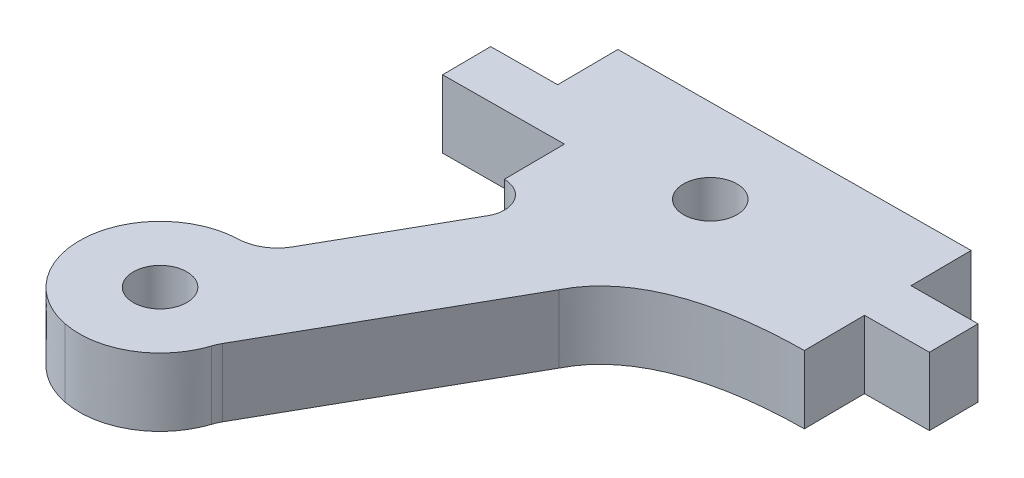
SolidWorks part; units mm, degrees
material "Acrylic (Medium-high impact)"
ref_plane "Front Plane" through (0, 0, 0) normal (0, 0, 1) x (1, 0, 0)
ref_plane "Top Plane" through (0, 0, 0) normal (0, 1, 0) x (1, 0, 0)
ref_plane "Right Plane" through (0, 0, 0) normal (1, 0, 0) x (0, 0, -1)
sketch "Sketch1" plane through (0, 0, 0) normal (0, 1, 0) x (1, 0, 0)
  line L0 (-5.4445, 9.8377) -> (-5.4416, 9.8377)
  line L1 (-5.4416, 9.8377) -> (-5.4208, 7.005)
  line L2 (-5.4208, 7.005) -> (-5.4208, 7.003)
  line L3 (-5.4208, 7.003) -> (-8.531, 6.9802)
  line L4 (-8.531, 6.9802) -> (-8.5144, 4.7142)
  line L5 (-8.5144, 4.7142) -> (-2.8595, 4.7556)
  line L6 (-2.8595, 4.7556) -> (-2.8388, 1.9229)
  line L7 (-1.7504, 0.0661) -> (-5.0527, -5.7627)
  line L8 (-2.7802, -11.3155) -> (2.9162, -1.2617)
  line L9 (14.1054, 4.8606) -> (14.0886, 7.1481)
  line L10 (14.0886, 7.1481) -> (10.9784, 7.1253)
  line L11 (10.9784, 7.1253) -> (10.9577, 9.9577)
  line L12 (10.9577, 9.9577) -> (-5.4445, 9.8377)
  line L13 (3.6635, 6.8214) -> (1.9104, 5.0391) construction
  line L14 (-7.4079, -9.6147) -> (-5.6288, -11.3711) construction
  line L15 (11.0897, 4.8386) -> (14.1054, 4.8606)
  line L16 (11.0897, 4.8386) -> (11.1104, 2.0059)
  circle A0 centre (2.7869, 5.9303) radius 1.25
  circle A1 centre (-6.5183, -10.4929) radius 1.25
  spline S0 degree 3 poles (-2.8388, 1.9229) (-2.3954, 1.9264) (-1.984, 1.6924) (-1.7594, 1.3093) knots 7 7 7 7 8 8 8 8
  spline S1 degree 3 poles (-1.7594, 1.3093) (-1.5349, 0.9265) (-1.5315, 0.4525) (-1.7504, 0.0661) knots 8 8 8 8 9 9 9 9
  spline S2 degree 3 poles (-5.0527, -5.7627) (-5.3774, -6.3357) (-5.9766, -6.6977) (-6.6341, -6.7181) knots 10 10 10 10 11 11 11 11
  spline S3 degree 3 poles (-6.6341, -6.7181) (-8.5475, -6.7772) (-10.1131, -8.2636) (-10.2745, -10.1746) knots 11 11 11 11 12 12 12 12
  spline S4 degree 3 poles (-10.2745, -10.1746) (-10.4358, -12.0857) (-9.1421, -13.8145) (-7.2656, -14.1949) knots 12 12 12 12 13 13 13 13
  spline S5 degree 3 poles (-7.2656, -14.1949) (-5.3893, -14.5752) (-3.5261, -13.4866) (-2.9333, -11.6629) knots 13 13 13 13 14 14 14 14
  spline S6 degree 3 poles (-2.9333, -11.6629) (-2.894, -11.5423) (-2.8428, -11.426) (-2.7802, -11.3155) knots 14 14 14 14 15 15 15 15
  spline S7 degree 3 poles (2.9162, -1.2617) (4.3849, 1.6595) (8.809, 1.9891) (11.1104, 2.0059) knots 16 16 16 16 17 17 17 17
  dimension "D1" = 2.5
extrude "Boss-Extrude1" add sketch "Sketch1" along normal blind 3.175
